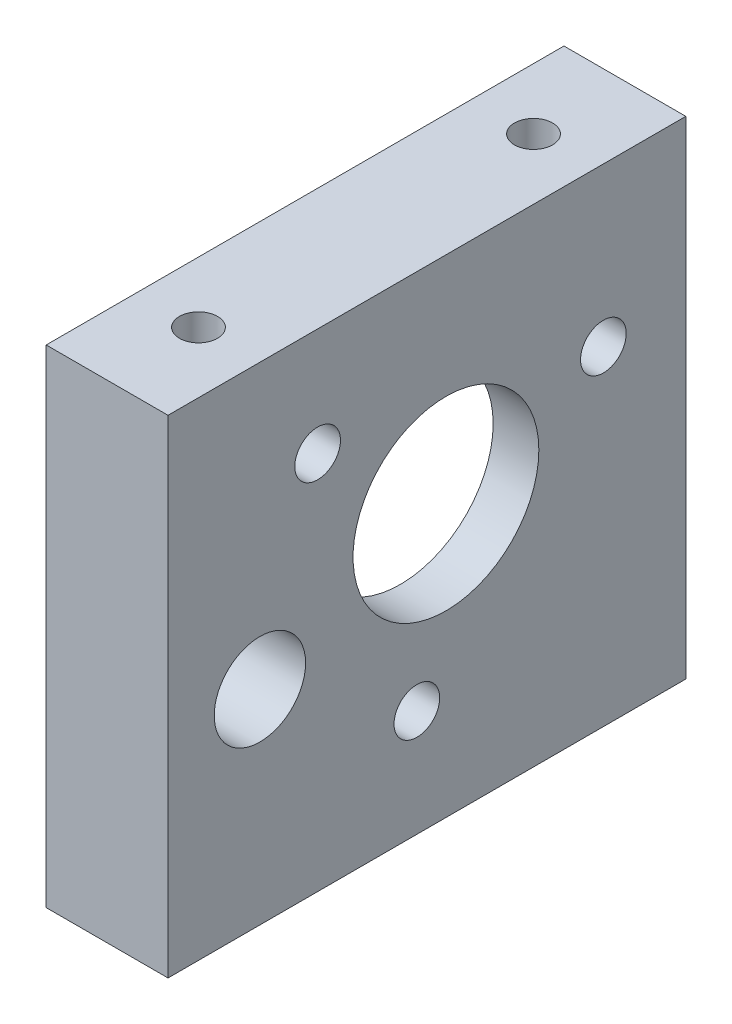
SolidWorks part; units mm, degrees
ref_plane "Front Plane" through (0, 0, 0) normal (0, 0, 1) x (1, 0, 0)
ref_plane "Top Plane" through (0, 0, 0) normal (0, 1, 0) x (1, 0, 0)
ref_plane "Right Plane" through (0, 0, 0) normal (1, 0, 0) x (0, 0, -1)
sketch "Sketch1" plane through (0, 0, 0) normal (1, 0, 0) x (0, 0, -1)
  line L1 (0, 0) -> (34, 0)
  line L2 (0, 0) -> (0, 32)
  line L3 (0, 32) -> (34, 32)
  line L4 (34, 0) -> (34, 32)
  dimension "D1" = 32
  dimension "D2" = 34
extrude "Boss-Extrude1" add sketch "Sketch1" along normal blind 8
sketch "Sketch2" plane through (8, 0, 0) normal (1, 0, 0) x (0, 0, -1)
  line L0 (28.5866, 21.6122) -> (6.034, 13.4037) construction
  line L1 (0, 0) -> (34, 0) construction
  line L2 (0, 32) -> (0, 0) construction
  circle A0 centre (18.25, 17.85) radius 6.1
  circle A1 centre (6.034, 13.4037) radius 3
  circle A2 centre (28.5866, 21.6122) radius 1.5
  dimension "D2" = 12.2
  dimension "D3" = 3
  dimension "D6" = 6
  dimension "D1" = 13
  dimension "D4" = 20
  dimension "D5" = 11
  dimension "D7" = 17.85
  dimension "D8" = 18.25
extrude "Cut-Extrude1" cut sketch "Sketch2" against normal up to next
pattern_circular "CirPattern1" count 3 over 360 about axis through (8, 17.85, -18.25) along (1, 0, 0) of face at (0, 21.6122, -27.0866)
sketch "Sketch3" plane through (0, 0, 0) normal (1, 0, 0) x (0, 0, -1)
  line L0 (32, 25) -> (32, 7)
  line L1 (29, 4) -> (15, 4)
  line L2 (12, 7) -> (12, 13.4037)
  line L3 (6, 21.8649) -> (6, 25)
  line L4 (9, 28) -> (29, 28)
  line L5 (34, 0) -> (34, 32) construction
  line L6 (0, 0) -> (34, 0) construction
  line L7 (34, 32) -> (0, 32) construction
  line L8 (0, 32) -> (0, 0) construction
  arc A0 (12, 13.4037) -> (8.0076, 19.0338) centre (6.034, 13.4037) ccw
  arc A1 (8.0076, 19.0338) -> (6, 21.8649) centre (9, 21.8649) cw
  arc A2 (15, 4) -> (12, 7) centre (15, 7) cw
  arc A3 (32, 7) -> (29, 4) centre (29, 7) cw
  arc A4 (32, 25) -> (29, 28) centre (29, 25) ccw
  arc A5 (6, 25) -> (9, 28) centre (9, 25) cw
  dimension "D4" = 3
  dimension "D5" = 3
  dimension "D1" = 2
  dimension "D2" = 4
  dimension "D3" = 4
  dimension "D6" = 6
  dimension "D7" = 12
extrude "Cut-Extrude2" cut sketch "Sketch3" along normal blind 5
hole_wizard "Tap Drill for M3x0.5 Tap1" positions "Sketch5" profile "Sketch4" hole size "M3x0.5" standard "ANSI Metric"
sketch "Sketch5" plane through (0, 32, 0) normal (0, 1, 0) x (-1, 0, 0)
  line L0 (0, -34) -> (0, 0) construction
  line L1 (-8, 0) -> (0, 0) construction
  line L2 (-8, -34) -> (0, -34) construction
  point P0 (-4, -6)
  point P2 (-4, -28)
  dimension "D1" = 4
  dimension "D2" = 6
  dimension "D3" = 6
sketch "Sketch4" plane through (4, 32, -6) normal (1, 0, 0) x (0, 0, 1)
  line L0 (0, 0) -> (0, 3.7511)
  line L1 (0, 3.7511) -> (1.25, 3)
  line L2 (1.25, 3) -> (1.25, 0)
  line L5 (1.25, 0) -> (0, 0)
  line L10 (0, 3.7511) -> (-1.25, 3) construction
  line L11 (0, -6.35) -> (0, 107.95) construction
  dimension "Hole Dia." = 2.5
  dimension "Hole Depth" = 3
  dimension "Drill Angle" = 118
hole_wizard "Tap Drill for M3x0.5 Tap2" positions "Sketch7" profile "Sketch6" hole size "M3x0.5" standard "ANSI Metric"
sketch "Sketch7" plane through (0, 0, 0) normal (0, -1, 0) x (1, 0, 0)
  line L0 (8, 0) -> (0, 0) construction
  line L1 (8, -34) -> (0, -34) construction
  line L2 (8, 0) -> (8, -34) construction
  point P0 (4, -6)
  point P2 (4, -28)
  dimension "D1" = 6
  dimension "D2" = 6
  dimension "D3" = 4
sketch "Sketch6" plane through (4, 0, -6) normal (1, 0, 0) x (0, 0, -1)
  line L0 (0, 0) -> (0, 3.7511)
  line L1 (0, 3.7511) -> (1.25, 3)
  line L2 (1.25, 3) -> (1.25, 0)
  line L5 (1.25, 0) -> (0, 0)
  line L10 (0, 3.7511) -> (-1.25, 3) construction
  line L11 (0, -6.35) -> (0, 107.95) construction
  dimension "Hole Dia." = 2.5
  dimension "Hole Depth" = 3
  dimension "Drill Angle" = 118
